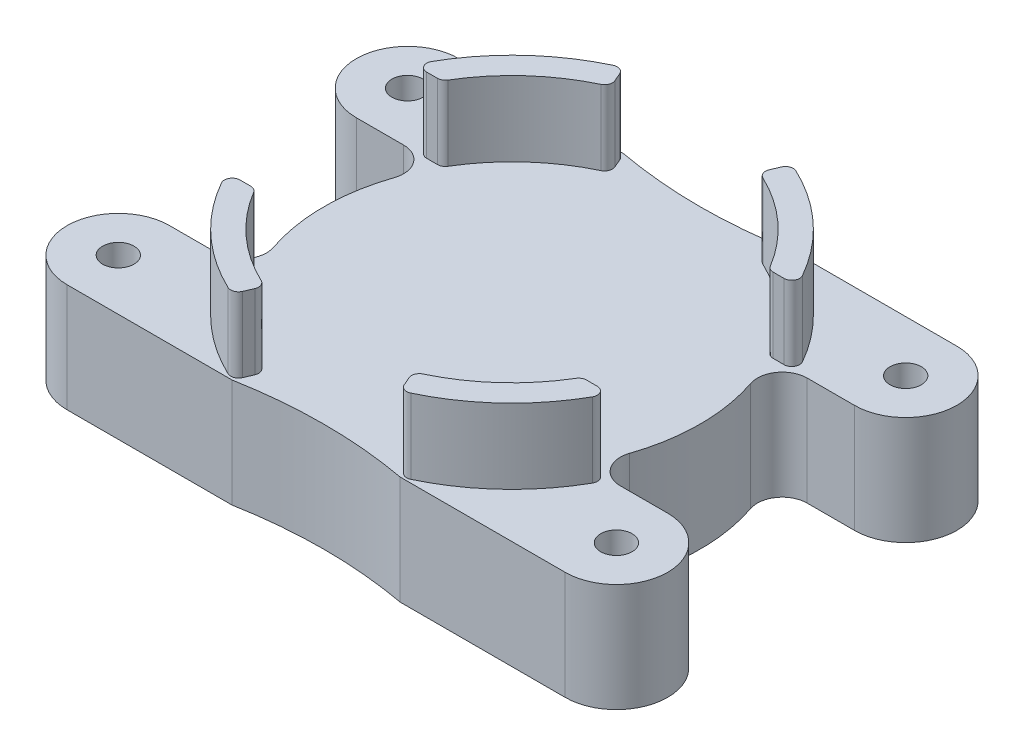
SolidWorks part; units mm, degrees
ref_plane "Front Plane" through (0, 0, 0) normal (0, 0, 1) x (1, 0, 0)
ref_plane "Top Plane" through (0, 0, 0) normal (0, 1, 0) x (1, 0, 0)
ref_plane "Right Plane" through (0, 0, 0) normal (1, 0, 0) x (0, 0, -1)
sketch "Sketch1" plane through (0, 0, 0) normal (0, 1, 0) x (1, 0, 0)
  line L0 (-25.4, 14.75) -> (-25.4, -14.75) construction
  line L1 (0, 0) -> (-25.4, 0) construction
  line L2 (-25.4, 14.75) -> (-15.9611, 14.75) construction
  line L3 (-25.4, 19.975) -> (-8.5626, 19.975)
  line L4 (-25.4, 9.525) -> (-19.5344, 9.525)
  line L5 (-25.4, -9.525) -> (-19.5344, -9.525)
  line L6 (-25.4, -19.975) -> (-8.5626, -19.975)
  line L7 (0, 0) -> (0, 18.796) construction
  line L8 (25.4, -19.975) -> (8.5626, -19.975)
  line L9 (25.4, -9.525) -> (19.5344, -9.525)
  line L10 (25.4, 9.525) -> (19.5344, 9.525)
  line L11 (25.4, 19.975) -> (8.5626, 19.975)
  circle A0 centre (0, 0) radius 18.796 construction
  circle A1 centre (0, 0) radius 19.1929
  circle A2 centre (0, 0) radius 21.7329
  circle A3 centre (-25.4, 14.75) radius 1.6
  circle A4 centre (-25.4, -14.75) radius 1.6
  arc A5 (-25.4, 19.975) -> (-25.4, 9.525) centre (-25.4, 14.75) ccw
  arc A7 (-25.4, -19.975) -> (-25.4, -9.525) centre (-25.4, -14.75) cw
  circle A8 centre (25.4, 14.75) radius 1.6
  circle A9 centre (25.4, -14.75) radius 1.6
  arc A10 (25.4, -19.975) -> (25.4, -9.525) centre (25.4, -14.75) ccw
  arc A11 (25.4, 19.975) -> (25.4, 9.525) centre (25.4, 14.75) cw
  dimension "D1" = 37.592
  dimension "D6" = 3.2
  dimension "D7" = 5.225
  dimension "D3" = 29.5
  dimension "D4" = 25.4
  dimension "D2" = 0.3969
  dimension "D5" = 2.54
extrude "Boss-Extrude1" add sketch "Sketch1" along normal blind 11.05 contours L3 A5 L4 A2 A3 | A2 A1 | A11 L11 A2 L10 A8 | L8 A10 L9 A2 A9 | A7 L6 A2 L5 A4 | A1 region at (-21.9725, 0, -15.4259) region at (0, 0, -21.1182) region at (21.9725, 0, -15.4259) region at (-21.9725, 0, 15.4259) region at (21.9725, 0, 15.4259) region at (0, 0, 0)
extrude "Boss-Extrude2" add sketch "Sketch1<3>" along normal blind 7.62 from surface contours A2 A1 region at (0, 0, -21.1182) starting at face at (-25.4, 11.05, -13.15)
sketch "Sketch1<3>" plane through (0, 0, 0) normal (0, 1, 0) x (1, 0, 0) same geometry as "Sketch1"
sketch "Sketch2" plane through (0, 18.67, 0) normal (0, 1, 0) x (1, 0, 0)
  line L1 (-19.5344, 9.525) -> (-16.6626, 9.525)
  line L2 (-19.5344, -9.525) -> (-16.6626, -9.525)
  line L3 (0, 0) -> (0, 19.1929) construction
  line L4 (0, 0) -> (-19.1929, 0) construction
  line L5 (19.5344, 9.525) -> (16.6626, 9.525)
  line L6 (19.5344, -9.525) -> (16.6626, -9.525)
  line L8 (-8.5626, 19.975) -> (0, 0) construction
  line L9 (0, 0) -> (8.5626, 19.975) construction
  line L10 (-8.5626, 19.975) -> (-7.5618, 17.6404)
  line L11 (8.5626, 19.975) -> (7.5618, 17.6404)
  line L12 (-8.5626, -19.975) -> (-7.5618, -17.6404)
  line L13 (8.5626, -19.975) -> (7.5618, -17.6404)
  circle A0 centre (0, 0) radius 21.7329 construction
  arc A1 (8.5626, 19.975) -> (-8.5626, 19.975) centre (0, 0) ccw
  circle A2 centre (0, 0) radius 19.1929 construction
  arc A3 (-16.6626, 9.525) -> (-16.6626, -9.525) centre (0, 0) ccw
  arc A4 (-19.5344, 9.525) -> (-19.5344, -9.525) centre (0, 0) ccw
  circle A5 centre (0, 0) radius 19.1929 construction
  arc A6 (19.5344, 9.525) -> (19.5344, -9.525) centre (0, 0) cw
  arc A7 (16.6626, 9.525) -> (16.6626, -9.525) centre (0, 0) cw
  arc A9 (-7.5618, 17.6404) -> (7.5618, 17.6404) centre (0, 0) cw
  arc A10 (8.5626, -19.975) -> (-8.5626, -19.975) centre (0, 0) cw
  arc A11 (-7.5618, -17.6404) -> (7.5618, -17.6404) centre (0, 0) ccw
extrude "Cut-Extrude1" cut sketch "Sketch2" against normal through all
fillet "Fillet2" radius 0.7937 16 edges at (7.5618, 14.86, -17.6404) (8.5626, 14.86, -19.975) (19.5344, 14.86, -9.525) (16.6626, 14.86, -9.525) (16.6626, 14.86, 9.525) (19.5344, 14.86, 9.525) (7.5618, 14.86, 17.6404) (8.5626, 14.86, 19.975) (-7.5618, 14.86, 17.6404) (-8.5626, 14.86, 19.975) (-16.6626, 14.86, 9.525) (-19.5344, 14.86, 9.525) (-16.6626, 14.86, -9.525) (-19.5344, 14.86, -9.525) (-7.5618, 14.86, -17.6404) (-8.5626, 14.86, -19.975) tangent propagation no
fillet "Fillet4" radius 2.54 1 edges at (16.6626, 5.525, 9.525) type face fillet first side face at (19.3499, 10.1925, 9.525) second side face at (17.9277, 5.525, 0)
fillet "Fillet5" radius 2.54 1 edges at (16.6626, 5.525, -9.525) type face fillet first side face at (19.3499, 10.1925, -9.525) second side face at (18.2615, 5.525, -1.7594)
fillet "Fillet6" radius 2.54 1 edges at (-16.6626, 5.525, -9.525) type face fillet first side face at (-19.3499, 10.1925, -9.525) second side face at (-17.9277, 5.525, 0)
fillet "Fillet7" radius 2.54 1 edges at (-16.6626, 5.525, 9.525) type face fillet first side face at (-19.3499, 10.1925, 9.525) second side face at (-18.2615, 5.525, 1.7594)
sketch "Sketch3" plane through (0, 11.05, 0) normal (0, 1, 0) x (1, 0, 0)
  line L0 (7.5618, 17.6404) -> (8.5626, 19.975) construction
  line L1 (7.5618, 17.6404) -> (8.5626, 19.975)
  line L2 (-8.5626, 19.975) -> (-7.5618, 17.6404) construction
  line L3 (-8.5626, 19.975) -> (-7.5618, 17.6404)
  line L4 (0, 0) -> (19.1929, 0) construction
  line L5 (-8.5626, -19.975) -> (-7.5618, -17.6404)
  line L6 (7.5618, -17.6404) -> (8.5626, -19.975)
  arc A0 (7.5618, 17.6404) -> (-7.5618, 17.6404) centre (0, 0) ccw construction
  arc A1 (7.5618, 17.6404) -> (-7.5618, 17.6404) centre (0, 0) ccw
  arc A2 (8.5626, 19.975) -> (-8.5626, 19.975) centre (0, 66.4554) cw
  arc A3 (18.1746, -6.1686) -> (18.1746, 6.1686) centre (0, 0) ccw construction
  arc A4 (8.5626, -19.975) -> (-8.5626, -19.975) centre (0, -66.4554) ccw
  arc A5 (7.5618, -17.6404) -> (-7.5618, -17.6404) centre (0, 0) cw
extrude "Boss-Extrude3" add sketch "Sketch3" against normal up to surface (11.05 mm away) contours L1 A2 A1 | A1 A2 L3 | L6 A5 A4 | A4 A5 L5 region at (6.053, 11.05, -18.9515) region at (-6.053, 11.05, -18.9515) region at (6.053, 11.05, 18.9515) region at (-6.053, 11.05, 18.9515) up to face at (0, 0, 0)
